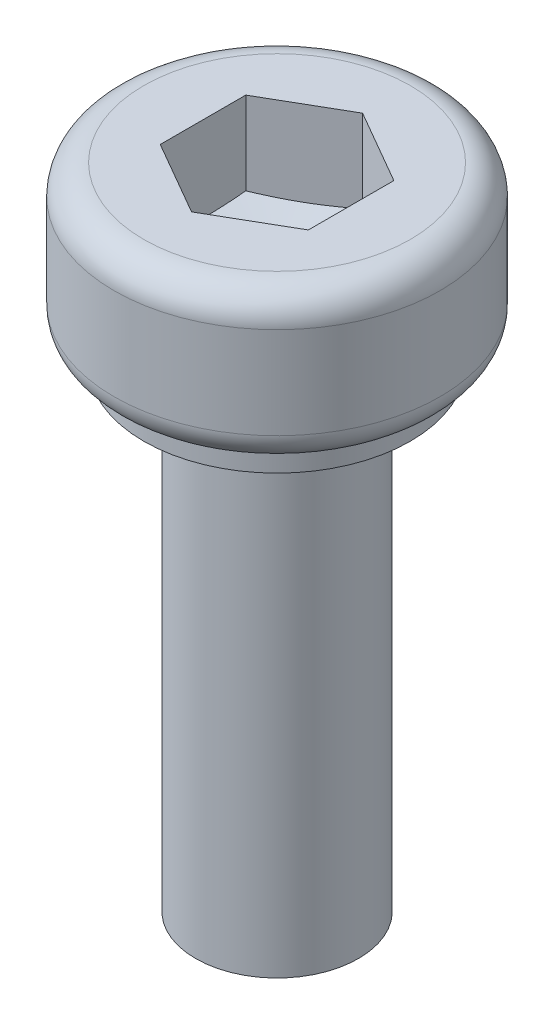
SolidWorks part; units mm, degrees
ref_plane "Front Plane" through (0, 0, 0) normal (0, 0, 1) x (1, 0, 0)
ref_plane "Top Plane" through (0, 0, 0) normal (0, 1, 0) x (1, 0, 0)
ref_plane "Right Plane" through (0, 0, 0) normal (1, 0, 0) x (0, 0, -1)
sketch "Sketch1" plane through (0, 0, 0) normal (0, 0, 1) x (1, 0, 0)
  line L0 (0, 4.0942) -> (0, -5.2249) construction
  line L1 (0, 5.475) -> (2.25, 5.475)
  line L2 (2.75, 4.975) -> (2.75, 3.425)
  line L3 (2.25, 2.525) -> (1.375, 2.525)
  line L4 (1.375, 2.525) -> (1.375, -5.475)
  line L5 (1.375, -5.475) -> (0, -5.475)
  line L6 (0, -5.475) -> (0, 5.475)
  line L7 (2.25, 2.525) -> (2.25, 2.925)
  line L8 (2.75, 2.525) -> (2.25, 2.525) construction
  line L9 (2.75, 3.425) -> (2.75, 2.525) construction
  line L10 (2.75, 5.475) -> (2.75, 4.975) construction
  line L11 (2.25, 5.475) -> (2.75, 5.475) construction
  arc A0 (2.25, 2.925) -> (2.75, 3.425) centre (2.25, 3.425) ccw
  arc A1 (2.25, 5.475) -> (2.75, 4.975) centre (2.25, 4.975) cw
  point P5 (0, 0)
  point P17 (0, 0)
  point P18 (0, 0)
  point P19 (2.25, 2.4541)
  dimension "D5" = 0.5
  dimension "D1" = 8
  dimension "D2" = 1.375
  dimension "D3" = 2.95
  dimension "D4" = 2.75
  dimension "D6" = 0.4
revolve "Revolve1" add sketch "Sketch1" angle 360 about L0
sketch "Sketch2" plane through (0, 5.475, 0) normal (0, 1, 0) x (1, 0, 0)
  line L1 (0, 1.4434) -> (-1.25, 0.7217)
  line L2 (-1.25, 0.7217) -> (-1.25, -0.7217)
  line L3 (-1.25, -0.7217) -> (0, -1.4434)
  line L4 (0, -1.4434) -> (1.25, -0.7217)
  line L5 (1.25, -0.7217) -> (1.25, 0.7217)
  line L6 (1.25, 0.7217) -> (0, 1.4434)
  circle A0 centre (0, 0) radius 1.25 construction
  dimension "D1" = 2.5
extrude "Boss-Extrude1" add sketch "Sketch2" against normal blind 2 separate body
sketch "Sketch3" plane through (0, 0, 0) normal (1, 0, 0) x (0, 0, -1)
  line L0 (0, 3.875) -> (0.4, 3.875)
  line L1 (0.4, 3.875) -> (1.4434, 4.075)
  line L2 (1.4434, 3.475) -> (1.4434, 5.475) construction
  line L3 (1.4434, 4.075) -> (1.4434, 3.475)
  line L4 (1.4434, 3.475) -> (0, 3.475)
  line L5 (-0.7217, 3.475) -> (0.7217, 3.475) construction
  line L6 (0, 3.475) -> (0, 3.875)
  line L7 (-0.7217, 5.475) -> (0.7217, 5.475) construction
  dimension "D1" = 1.6
  dimension "D2" = 1.4
  dimension "D3" = 0.4
revolve "Cut-Revolve1" cut sketch "Sketch3" angle 360 about L6
combine bodies "Combine1" operation type subtract main body 101 bodies to subtract 104
equation "\"Length\"= 8mm"
equation "\"D1@Sketch1\"=\"Length\""
equation "\"ThreadDiam\"= 2.75"
equation "\"D2@Sketch1\"=\"ThreadDiam\"/2"
equation "\"HeadHeight\"=2.95"
equation "\"D3@Sketch1\"=\"HeadHeight\""
equation "\"HeadDiam\"= 5.5"
equation "\"D4@Sketch1\"=\"HeadDiam\"/2"
equation "\"HexSize\"=2.5"
equation "\"D1@Sketch2\"=\"HexSize\""
